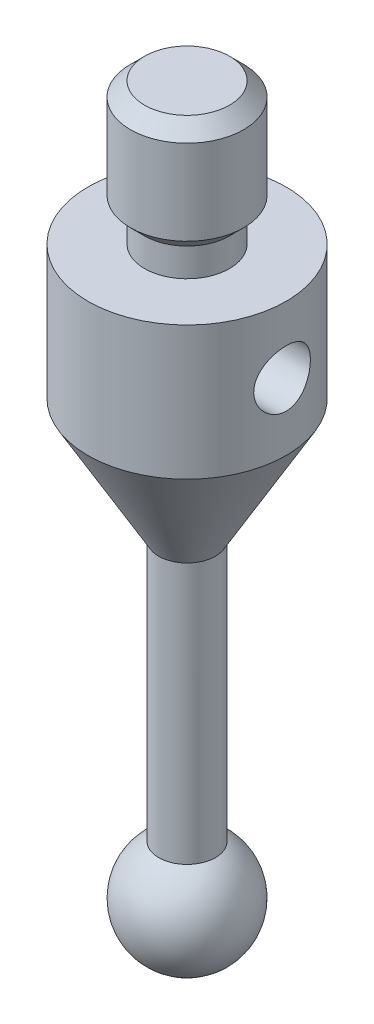
SolidWorks part; units mm, degrees
ref_plane "Front Plane" through (0, 0, 0) normal (0, 0, 1) x (1, 0, 0)
ref_plane "Top Plane" through (0, 0, 0) normal (0, 1, 0) x (1, 0, 0)
ref_plane "Right Plane" through (0, 0, 0) normal (1, 0, 0) x (0, 0, -1)
sketch "Sketch1" plane through (0, 0, 0) normal (0, 0, 1) x (1, 0, 0)
  line L0 (0, 0) -> (0, -2)
  line L1 (0, 0) -> (0, 2)
  arc A0 (0, 2) -> (0, -2) centre (0, 0) cw
  dimension "D1" = 4
revolve "Revolve1" add sketch "Sketch1" angle 360 about L1
sketch "Sketch2" plane through (0, 0, 0) normal (0, 1, 0) x (1, 0, 0)
  circle A1 centre (0, 0) radius 1
  dimension "D2" = 2
extrude "Boss-Extrude2" add sketch "Sketch2" along normal blind 10 contours A1
sketch "Sketch4" plane through (0, 10, 0) normal (0, 1, 0) x (1, 0, 0)
  circle A0 centre (0, 0) radius 3.5
  dimension "D1" = 7
extrude "Boss-Extrude3" add sketch "Sketch4" along normal blind 10
chamfer "Chamfer1" distance 3.05 angle 60 1 edges at (0, 10, 3.5) first distance on face at (0, 10, 1)
sketch "Sketch5" plane through (0, 0, 0) normal (1, 0, 0) x (0, 0, -1)
  line L0 (0, 20) -> (0, 15.2828) construction
  line L1 (3.5, 20) -> (-3.5, 20) construction
  line L2 (-3.5, 15.2828) -> (3.5, 15.2828) construction
  circle A0 centre (0, 17.6414) radius 1
  dimension "D1" = 2
extrude "Cut-Extrude4" cut sketch "Sketch5" against normal through all both and the other way through all
sketch "Sketch6" plane through (0, 20, 0) normal (0, 1, 0) x (1, 0, 0)
  circle A0 centre (0, 0) radius 1.5
  dimension "D1" = 3
extrude "Boss-Extrude4" add sketch "Sketch6" along normal blind 1
sketch "Sketch7" plane through (0, 21, 0) normal (0, 1, 0) x (1, 0, 0)
  circle A0 centre (0, 0) radius 2
  dimension "D1" = 4
extrude "Boss-Extrude5" add sketch "Sketch7" along normal blind 4
chamfer "Chamfer2" distance 0.5 angle 45 2 edges at (0, 25, 2) (0, 21, 2)
